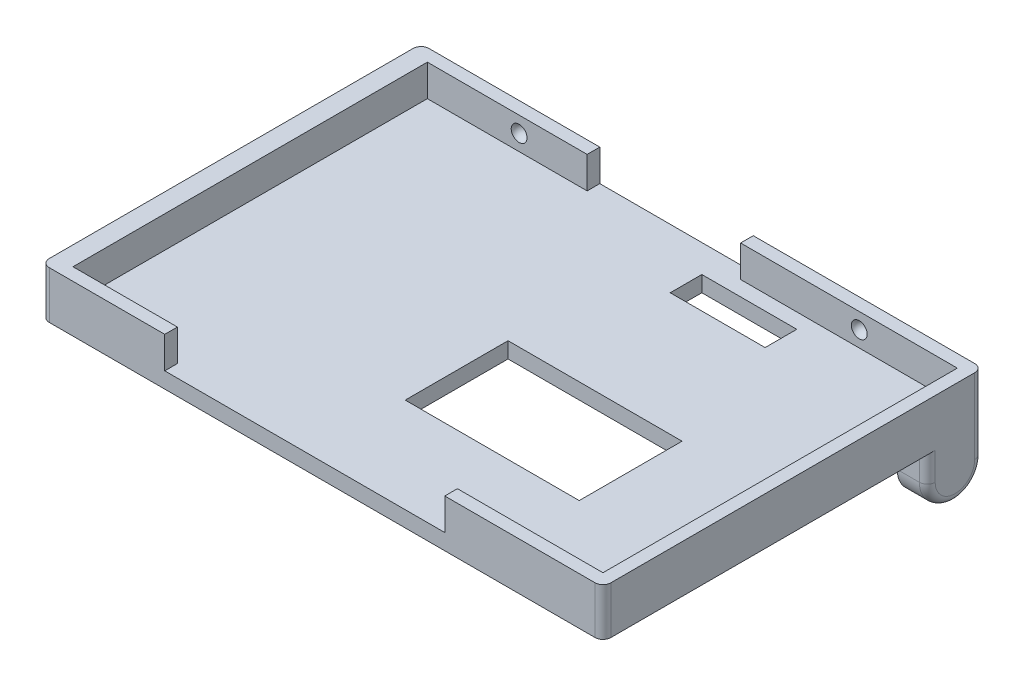
SolidWorks part; units mm, degrees
ref_plane "前视基准面" through (0, 0, 0) normal (0, 0, 1) x (1, 0, 0)
ref_plane "上视基准面" through (0, 0, 0) normal (0, 1, 0) x (1, 0, 0)
ref_plane "右视基准面" through (0, 0, 0) normal (1, 0, 0) x (0, 0, -1)
sketch "草图1" plane through (0, 0, 0) normal (0, 1, 0) x (1, 0, 0)
  line L1 (-17.75, 12) -> (17.75, 12)
  line L2 (-17.75, 12) -> (-17.75, -12)
  line L3 (-17.75, -12) -> (17.75, -12)
  line L4 (17.75, 12) -> (17.75, -12)
  line L5 (-17.75, 12) -> (17.75, -12) construction
  line L6 (-17.75, -12) -> (17.75, 12) construction
  point P0 (0, 0)
  dimension "D1" = 24
  dimension "D2" = 35.5
extrude "凸台-拉伸1" add sketch "草图1" along normal blind 3
sketch "草图2" plane through (0, 3, 0) normal (0, 1, 0) x (1, 0, 0)
  line L0 (17.75, 12) -> (-17.75, 12) construction
  line L1 (-15.75, 10) -> (15.75, 10)
  line L2 (-15.75, 10) -> (-15.75, -10)
  line L3 (-15.75, -10) -> (15.75, -10)
  line L4 (15.75, 10) -> (15.75, -10)
  line L5 (-15.75, 10) -> (15.75, -10) construction
  line L6 (-15.75, -10) -> (15.75, 10) construction
  line L7 (-17.75, 12) -> (-17.75, -12) construction
  point P0 (0, 0)
  dimension "D1" = 2
  dimension "D2" = 2
extrude "切除-拉伸1" cut sketch "草图2" against normal blind 2
sketch "草图4" plane through (0, 0, 0) normal (0, -1, 0) x (1, 0, 0)
  line L1 (-17.75, -12) -> (-15.85, -12)
  line L2 (-17.75, -12) -> (-17.75, -8.5)
  line L3 (-17.75, -8.5) -> (-15.85, -8.5)
  line L4 (-15.85, -12) -> (-15.85, -8.5)
  line L5 (17.75, -12) -> (15.85, -12)
  line L6 (17.75, -12) -> (17.75, -8.5)
  line L7 (17.75, -8.5) -> (15.85, -8.5)
  line L8 (15.85, -12) -> (15.85, -8.5)
  dimension "D1" = 3.5
  dimension "D2" = 1.9
  dimension "D3" = 1.9
  dimension "D4" = 3.5
extrude "凸台-拉伸2" add sketch "草图4" along normal blind 3.5
sketch "草图5" plane through (-17.75, 0, 0) normal (-1, 0, 0) x (0, 0, 1)
  line L1 (-12, 3) -> (-12, -3.5) construction
  line L2 (-12, -1.75) -> (-12, -3.5)
  line L5 (-10.25, -3.5) -> (-12, -3.5)
  arc A1 (-12, -1.75) -> (-10.25, -3.5) centre (-10.25, -1.75) ccw
  dimension "D1" = 1.75
extrude "切除-拉伸3" cut sketch "草图5" against normal blind 2
sketch "草图6" plane through (-17.75, 0, 0) normal (-1, 0, 0) x (0, 0, 1)
  line L0 (-8.5, -3.5) -> (-10.25, -3.5)
  line L1 (-8.5, -3.5) -> (-10.25, -3.5) construction
  line L2 (-8.5, -3.5) -> (-8.5, 0) construction
  line L3 (-8.5, -3.5) -> (-8.5, -1.75)
  arc A0 (-12, -1.75) -> (-10.25, -3.5) centre (-10.25, -1.75) ccw construction
  arc A1 (-10.25, -3.5) -> (-8.5, -1.75) centre (-10.25, -1.75) ccw
extrude "切除-拉伸4" cut sketch "草图6" against normal blind 2
sketch "草图7" plane through (17.75, 0, 0) normal (1, 0, 0) x (0, 0, -1)
  line L0 (8.5, -3.5) -> (10.25, -3.5)
  line L1 (12, -3.5) -> (8.5, -3.5) construction
  line L2 (8.5, -3.5) -> (8.5, 0) construction
  line L3 (8.5, -1.75) -> (8.5, -3.5)
  arc A0 (10.25, -3.5) -> (8.5, -1.75) centre (10.25, -1.75) cw
extrude "切除-拉伸5" cut sketch "草图7" against normal blind 2
sketch "草图8" plane through (17.75, 0, 0) normal (1, 0, 0) x (0, 0, -1)
  line L0 (12, -3.5) -> (10.25, -3.5)
  line L1 (12, 3) -> (12, -3.5) construction
  line L2 (12, -1.75) -> (12, -3.5)
  arc A0 (10.25, -3.5) -> (12, -1.75) centre (10.25, -1.75) ccw
extrude "切除-拉伸6" cut sketch "草图8" against normal blind 2
sketch "草图10" plane through (15.85, 0, 0) normal (-1, 0, 0) x (0, 0, 1)
  line L0 (-8.5, -1.75) -> (-8.5, 0) construction
  line L1 (12, 0) -> (-8.5, 0) construction
  circle A0 centre (-10.25, -1.75) radius 0.6
  dimension "D1" = 1.2
  dimension "D2" = 1.75
  dimension "D3" = 1.75
extrude "切除-拉伸8" cut sketch "草图10" against normal blind 1.5
sketch "草图11" plane through (0, 0, 0) normal (0, -1, 0) x (1, 0, 0)
  line L0 (17.75, 12) -> (17.75, -8.5) construction
  line L1 (1.75, -8.25) -> (7.75, -8.25)
  line L2 (1.75, -8.25) -> (1.75, -10.25)
  line L3 (1.75, -10.25) -> (7.75, -10.25)
  line L4 (7.75, -8.25) -> (7.75, -10.25)
  line L6 (15.85, -12) -> (-15.85, -12) construction
  dimension "D1" = 10
  dimension "D2" = 6
  dimension "D3" = 2
  dimension "D4" = 1.75
extrude "切除-拉伸9" cut sketch "草图11" against normal blind 2
sketch "草图12" plane through (-15.85, 0, 0) normal (1, 0, 0) x (0, 0, -1)
  line L0 (12, -1.75) -> (12, 0) construction
  line L1 (12, 0) -> (8.5, 0) construction
  circle A0 centre (10.25, -1.75) radius 0.6
  dimension "D1" = 1.2
  dimension "D2" = 1.75
  dimension "D3" = 1.75
extrude "切除-拉伸10" cut sketch "草图12" against normal blind 1.5
sketch "草图13" plane through (0, 3, 0) normal (0, 1, 0) x (1, 0, 0)
  line L1 (-15.6782, 11.2) -> (16.95, 11.2)
  line L2 (16.95, 11.2) -> (16.95, -11.2)
  line L3 (16.95, -11.2) -> (-15.75, -11.2)
  line L7 (17.75, 12) -> (-17.75, 12) construction
  line L10 (17.75, -12) -> (17.75, 12) construction
  line L11 (-17.75, -12) -> (17.75, -12) construction
  line L12 (-15.6782, 11.2) -> (-16.55, 11.2)
  line L13 (-16.55, 11.2) -> (-16.55, -11.2)
  line L14 (-16.55, -11.2) -> (-15.75, -11.2)
  line L15 (-17.75, 12) -> (-17.75, -12) construction
  dimension "D1" = 1.2
  dimension "D2" = 0.8
  dimension "D3" = 0.8
  dimension "D4" = 0.8
extrude "切除-拉伸11" cut sketch "草图13" against normal blind 2
sketch "草图14" plane through (0, 0, -11.2) normal (0, 0, 1) x (1, 0, 0)
  line L0 (16.95, 1) -> (-16.55, 1) construction
  line L2 (-17.75, 3) -> (-17.75, -1.75) construction
  line L3 (-11.25, 2) -> (-10.25, 2)
  line L5 (10.25, 2) -> (11.25, 2)
  line L7 (17.75, 3) -> (17.75, -1.75) construction
  arc A2 (-11.25, 2) -> (-10.25, 2) centre (-10.75, 2) cw
  arc A3 (10.25, 2) -> (11.25, 2) centre (10.75, 2) cw
  dimension "D1" = 7
  dimension "D4" = 1
  dimension "D7" = 0.5
  dimension "D6" = 0.5
  dimension "D2" = 1
  dimension "D3" = 1
  dimension "D5" = 1
  dimension "D8" = 7
revolve "切除-旋转1" cut sketch "草图14" angle 360 about L5
sketch "草图15" plane through (0, 0, 11.2) normal (0, 0, -1) x (-1, 0, 0)
  line L0 (10.25, 2) -> (11.25, 2)
  line L1 (16.55, 1) -> (-16.95, 1) construction
  line L2 (17.75, 3) -> (17.75, 0) construction
  line L3 (-11.25, 2) -> (-10.25, 2)
  line L5 (-17.75, 3) -> (-17.75, 0) construction
  arc A2 (10.25, 2) -> (11.25, 2) centre (10.75, 2) cw
  arc A3 (-11.25, 2) -> (-10.25, 2) centre (-10.75, 2) cw
  dimension "D1" = 1
  dimension "D2" = 0.5
  dimension "D6" = 0.5
  dimension "D3" = 1
  dimension "D4" = 7
  dimension "D5" = 1
  dimension "D7" = 7
revolve "切除-旋转2" cut sketch "草图15" angle 360 about L3
sketch "草图16" plane through (15.85, 0, 0) normal (-1, 0, 0) x (0, 0, 1)
  line L1 (-10.5, -0.5) -> (-10, -0.5)
  line L2 (-8.5, -1.75) -> (-8.5, 0) construction
  arc A3 (-10.5, -0.5) -> (-10, -0.5) centre (-10.25, -0.5) cw
  circle A4 centre (-10.25, -1.75) radius 0.6 construction
  dimension "D4" = 0.25
  dimension "D1" = 0.5
  dimension "D2" = 1.75
  dimension "D3" = 1.25
revolve "切除-旋转3" cut sketch "草图16" angle 360 about L1
pattern_circular "阵列(圆周)3" count 8 over 360 about axis through (17.35, -1.75, -10.25) along (-1, 0, 0) of "切除-旋转3"
sketch "草图17" plane through (0, 3, 0) normal (0, 1, 0) x (1, 0, 0)
  line L0 (17.75, 12) -> (-17.75, 12) construction
  line L1 (16.95, 11.2) -> (-16.55, 11.2) construction
  line L2 (-6.45, 12) -> (3.25, 12)
  line L3 (-6.45, 12) -> (-6.45, 11.2)
  line L4 (-6.45, 11.2) -> (3.25, 11.2)
  line L5 (3.25, 12) -> (3.25, 11.2)
  line L6 (-17.75, 12) -> (-17.75, -12) construction
  line L7 (17.75, -12) -> (17.75, 12) construction
  dimension "D1" = 11.3
  dimension "D2" = 14.5
extrude "切除-拉伸12" cut sketch "草图17" against normal blind 2
sketch "草图18" plane through (0, 3, 0) normal (0, 1, 0) x (1, 0, 0)
  line L0 (-16.55, -11.2) -> (16.95, -11.2) construction
  line L1 (-9.95, -11.2) -> (7.75, -11.2)
  line L2 (-9.95, -11.2) -> (-9.95, -12)
  line L3 (-9.95, -12) -> (7.75, -12)
  line L4 (7.75, -11.2) -> (7.75, -12)
  line L5 (-17.75, -12) -> (17.75, -12) construction
  line L6 (-17.75, 12) -> (-17.75, -12) construction
  line L7 (17.75, -12) -> (17.75, 12) construction
  dimension "D1" = 7.8
  dimension "D2" = 10
extrude "切除-拉伸13" cut sketch "草图18" against normal blind 2
sketch "草图19" plane through (0, 0, 0) normal (0, -1, 0) x (1, 0, 0)
  line L0 (17.75, 12) -> (17.75, -8.5) construction
  line L1 (-0.75, 6) -> (10.25, 6)
  line L2 (-0.75, 6) -> (-0.75, -0.5)
  line L3 (-0.75, -0.5) -> (10.25, -0.5)
  line L4 (10.25, 6) -> (10.25, -0.5)
  line L5 (-17.75, 12) -> (17.75, 12) construction
  dimension "D1" = 6.5
  dimension "D2" = 11
  dimension "D3" = 7.5
  dimension "D4" = 6
extrude "切除-拉伸14" cut sketch "草图19" against normal blind 1
fillet "圆角1" radius 0.5 8 edges at (17.75, -0.875, -8.5) (17.75, -3.5, -10.25) (-17.75, -0.875, -8.5) (-17.75, -3.5, -10.25) (17.75, 1.5, 12) (17.75, 0.625, -12) (-17.75, 0.625, -12) (-17.75, 1.5, 12)
